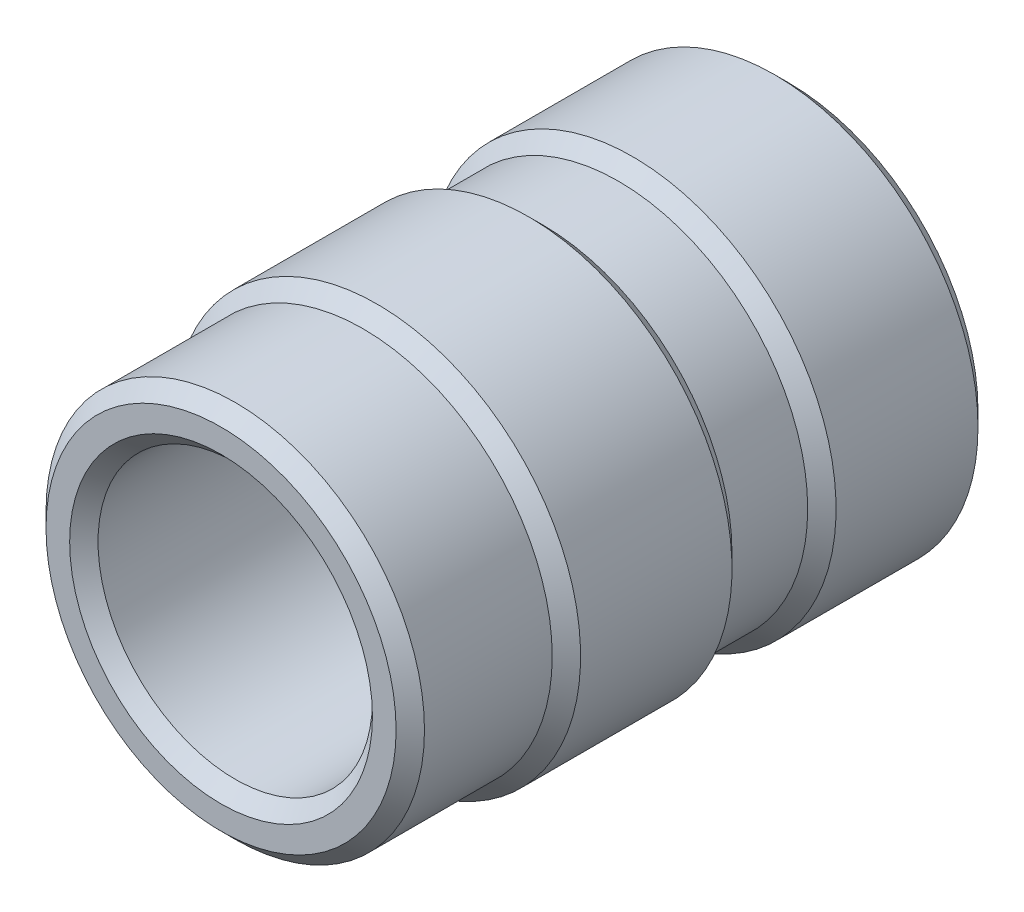
SolidWorks part; units mm, degrees
ref_plane "Front" through (0, 0, 0) normal (0, 0, 1) x (1, 0, 0)
ref_plane "Top" through (0, 0, 0) normal (0, 1, 0) x (1, 0, 0)
ref_plane "Right" through (0, 0, 0) normal (1, 0, 0) x (0, 0, -1)
sketch "Skizze1" plane through (0, 0, 0) normal (0, 0, 1) x (1, 0, 0)
  circle A0 centre (0, 0) radius 2
  circle A1 centre (0, 0) radius 1.45
  dimension "D1" = 4
  dimension "D2" = 2.9
extrude "Aufsatz-Linear austragen1" add sketch "Skizze1" along normal blind 6
cosmetic thread "Gewindedarstellung1"
sketch "Skizze2" plane through (0, 0, 0) normal (0, 0, -1) x (-1, 0, 0)
  circle A0 centre (0, 0) radius 2.15
  circle A1 centre (0, 0) radius 1.7557
  dimension "D1" = 4.3
extrude "Aufsatz-Linear austragen2" add sketch "Skizze2" against normal blind 1.8
extrude "Aufsatz-Linear austragen3" add sketch "Skizze2<2>" against normal blind 1.9 from offset 2.6 offset against normal yes
sketch "Skizze2<2>" plane through (0, 0, 0) normal (0, 0, -1) x (-1, 0, 0) same geometry as "Skizze2"
chamfer "Fase1" distance 0.15 angle 45 4 edges at (1.45, 0, 0) (1.45, 0, 6) (2, 0, 6) (-2.15, 0, 0)
chamfer "Fase2" distance 0.15 angle 45 3 edges at (-2.15, 0, 4.5) (-2.15, 0, 2.6) (-2.15, 0, 1.8)
